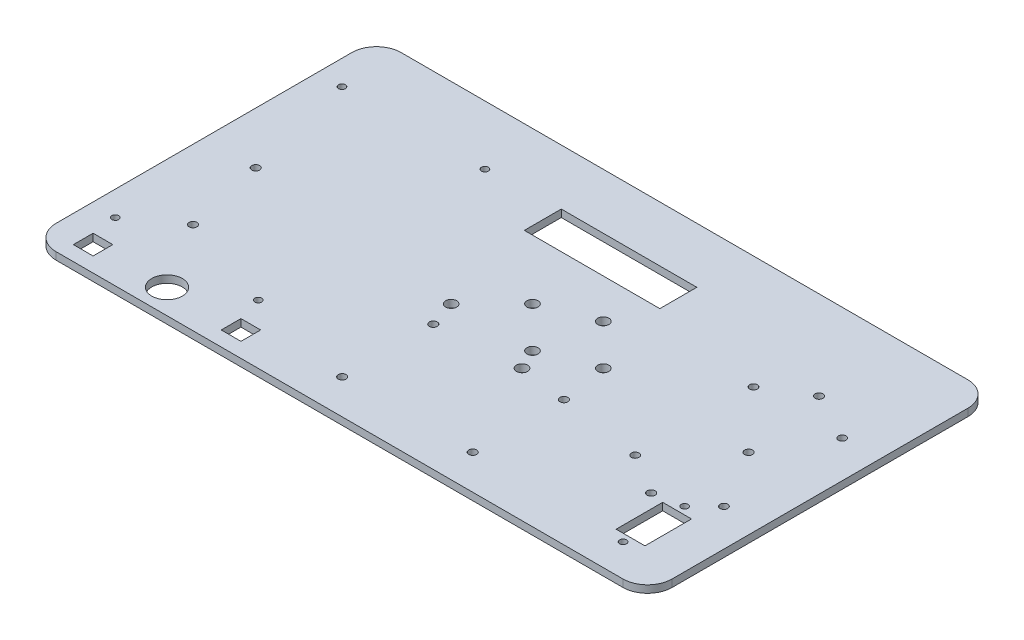
SolidWorks part; units mm, degrees
ref_plane "Front Plane" through (0, 0, 0) normal (0, 0, 1) x (1, 0, 0)
ref_plane "Top Plane" through (0, 0, 0) normal (0, 1, 0) x (1, 0, 0)
ref_plane "Right Plane" through (0, 0, 0) normal (1, 0, 0) x (0, 0, -1)
sketch "Sketch1" plane through (0, 0, 0) normal (0, 1, 0) x (1, 0, 0)
  line L1 (125, -70) -> (-125, -70)
  line L2 (125, -70) -> (125, 70)
  line L3 (125, 70) -> (-125, 70)
  line L4 (-125, -70) -> (-125, 70)
  line L5 (125, -70) -> (-125, 70) construction
  line L6 (125, 70) -> (-125, -70) construction
  point P0 (0, 0)
extrude "Boss-Extrude1" add sketch "Sketch1" along normal blind 3 contours L3 L4 L1 L2
fillet "Fillet2" radius 10 4 edges at (-125, 1.5, 70) (125, 1.5, 70) (-125, 1.5, -70) (125, 1.5, -70)
sketch "Sketch2" plane through (0, 0, 0) normal (0, 1, 0) x (1, 0, 0)
  line L0 (-125, 0) -> (125, 0)
  line L1 (-125, -60) -> (-125, 60) construction
  line L2 (125, -60) -> (125, 60) construction
  line L3 (110, -24) -> (110, 24)
  line L4 (-115, -46) -> (-115, 46)
  line L5 (110, 24) -> (74, 24)
  line L6 (110, 24) -> (110, -24)
  line L7 (110, -24) -> (74, -24)
  line L8 (74, 24) -> (74, -24)
  line L14 (0, 0.0606) -> (0, -55.9394)
  line L15 (37, -16.4394) -> (37, 16.5606)
  line L17 (96, 0) -> (-104, 0)
  line L18 (0, 0.0606) -> (37, 0.0606)
  line L20 (0, -55.9394) -> (-13, -55.9394)
  line L22 (0, -55.9394) -> (40, -55.9394)
  line L23 (-13, -55.9394) -> (-13, -18.9394)
  line L24 (37, 16.5606) -> (20.5, 16.5606)
  line L25 (-13, -18.9394) -> (40, -18.9394)
  line L26 (-13, -18.9394) -> (-13, -55.9394)
  line L27 (-13, -55.9394) -> (40, -55.9394)
  line L28 (40, -18.9394) -> (40, -55.9394)
  line L29 (37, 16.5606) -> (37, -16.4394)
  line L30 (37, -16.4394) -> (20.5, -16.4394)
  line L31 (20.5, 16.5606) -> (20.5, -16.4394)
  line L32 (0, -8.1894) -> (0, 8.3106)
  line L33 (16.5, 8.3106) -> (-16.5, 8.3106)
  line L34 (-115, 46) -> (-57, 46)
  line L35 (-115, 46) -> (-115, -46)
  line L36 (-115, -46) -> (-57, -46)
  line L37 (-57, 46) -> (-57, -46)
  line L39 (16.5, -8.1894) -> (-16.5, -8.1894)
  line L40 (16.5, -8.1894) -> (16.5, 8.3106)
  line L41 (16.5, 8.3106) -> (-16.5, 8.3106)
  line L42 (-16.5, -8.1894) -> (-16.5, 8.3106)
  line L43 (16.5, -8.1894) -> (-16.5, 8.3106) construction
  line L44 (16.5, 8.3106) -> (-16.5, -8.1894) construction
  circle A0 centre (110, 24) radius 1.55
  circle A1 centre (74, 24) radius 1.55
  circle A2 centre (74, -24) radius 1.55
  circle A3 centre (110, -24) radius 1.55
  circle A8 centre (-13, -18.9394) radius 1.6
  circle A9 centre (-13, -55.9394) radius 1.6
  circle A10 centre (40, -18.9394) radius 1.6
  circle A11 centre (40, -55.9394) radius 1.6
  circle A12 centre (37, 0.0606) radius 2.25
  circle A13 centre (20.5, 16.5606) radius 2.25
  circle A14 centre (20.5, -16.4394) radius 2.25
  circle A15 centre (96, 0) radius 1.6
  circle A16 centre (-104, 0) radius 1.6
  circle A17 centre (-115, 46) radius 1.4
  circle A18 centre (-57, 46) radius 1.4
  circle A19 centre (-57, -46) radius 1.4
  circle A20 centre (-115, -46) radius 1.4
  circle A21 centre (-16.5, -8.1894) radius 2.25
  circle A22 centre (16.5, -8.1894) radius 2.25
  circle A23 centre (0, 8.3106) radius 2.25
  point P6 (110, 0)
  point P10 (110, 0)
  point P16 (-115, 0)
  point P20 (-115, 0)
  point P25 (-115, 0)
  point P26 (74, 0)
  point P41 (37, 0.0606)
  point P46 (96, 0)
  point P55 (0, 0.0606)
  point P58 (0, 8.3106)
  dimension "D1" = 200
  dimension "D2" = 53
  dimension "D3" = 37
  dimension "D4" = 48
  dimension "D5" = 36
  dimension "D6" = 16.5
  dimension "D7" = 33
sketch "Sketch3" plane through (0, 0, 0) normal (0, 1, 0) x (1, 0, 0)
  line L1 (115, -70) -> (-115, -70) construction
  line L2 (-125, -60) -> (-125, 60) construction
  circle A3 centre (-104, 0) radius 33.5
  circle A4 centre (96, 0) radius 195.5
  circle A5 centre (-96.745, -32.705) radius 1.6
  point P6 (-338.6726, 198.929)
  point P7 (-96.745, -32.705)
  dimension "D1" = 37.295
  dimension "D2" = 28.255
sketch "Sketch4" plane through (0, 3, 0) normal (0, 1, 0) x (1, 0, 0)
  line L2 (115, -70) -> (-115, -70) construction
  line L3 (125, -60) -> (125, 60) construction
  line L4 (115, 70) -> (-115, 70) construction
  circle A4 centre (96, 0) radius 34.5
  circle A5 centre (-104, 0) radius 197.5
  circle A6 centre (90.54, -34.0652) radius 1.6
  circle A7 centre (90.54, 34.0652) radius 1.6
  point P4 (90.54, 34.0652)
  point P5 (90.54, 34.0652)
  point P6 (90.54, 34.0652)
  point P7 (96, 0)
  point P8 (90.54, 34.0652)
  point P9 (-104, 0)
  point P10 (90.54, 34.0652)
  point P11 (90.54, 34.0652)
  point P13 (90.54, -34.0652)
  dimension "D1" = 35.9348
  dimension "D2" = 34.46
  dimension "D3" = 34.46
  dimension "D4" = 35.9348
sketch "Sketch5" plane through (0, 3, 0) normal (0, 1, 0) x (1, 0, 0)
  line L0 (110, -24) -> (110, -58)
  line L1 (94, -44.446) -> (110, -44.446)
  line L2 (110, -58) -> (94, -58)
  line L3 (110, -58) -> (110, -30.892)
  line L4 (110, -30.892) -> (94, -30.892)
  line L5 (94, -58) -> (94, -30.892)
  line L6 (102, -31.946) -> (102, -56.946)
  line L7 (-125, -60) -> (-80, -60)
  line L8 (107.85, -53.896) -> (96.15, -53.896)
  line L9 (107.85, -53.896) -> (107.85, -34.996)
  line L10 (107.85, -34.996) -> (96.15, -34.996)
  line L11 (96.15, -53.896) -> (96.15, -34.996)
  line L12 (107.85, -53.896) -> (96.15, -34.996) construction
  line L13 (107.85, -34.996) -> (96.15, -53.896) construction
  line L14 (0, 70) -> (0, 40)
  line L15 (115, 70) -> (-115, 70) construction
  line L16 (-80, -60) -> (-50, -60)
  line L17 (-27.5, 47.5) -> (27.5, 47.5)
  line L18 (-27.5, 47.5) -> (-27.5, 32.5)
  line L19 (-27.5, 32.5) -> (27.5, 32.5)
  line L20 (27.5, 47.5) -> (27.5, 32.5)
  line L21 (-27.5, 47.5) -> (27.5, 32.5) construction
  line L22 (-27.5, 32.5) -> (27.5, 47.5) construction
  line L24 (-114, -56) -> (-106, -56)
  line L25 (-114, -56) -> (-114, -64)
  line L26 (-114, -64) -> (-106, -64)
  line L27 (-106, -56) -> (-106, -64)
  line L28 (-114, -56) -> (-106, -64) construction
  line L29 (-114, -64) -> (-106, -56) construction
  line L30 (-54, -56) -> (-46, -56)
  line L31 (-54, -56) -> (-54, -64)
  line L32 (-54, -64) -> (-46, -64)
  line L33 (-46, -56) -> (-46, -64)
  line L34 (-54, -56) -> (-46, -64) construction
  line L35 (-54, -64) -> (-46, -56) construction
  circle A0 centre (102, -31.946) radius 1.4
  circle A1 centre (102, -56.946) radius 1.4
  circle A3 centre (-80, -60) radius 6.2
  point P11 (102, -44.446)
  point P13 (102, -44.446)
  point P31 (-110, -60)
  point P34 (-110, -60)
extrude "Cut-Extrude5" cut sketch "Sketch2" against normal blind 7 and the other way blind 7 contours A17 | A18 | A20 | A19 | A16 | A23 | A21 | A22 | A13 | A12 | A10 | A14 | A8 | A9 | A11 | A1 | A0 | A15 | A3 | A2
extrude "Cut-Extrude6" cut sketch "Sketch3" against normal blind 7 and the other way blind 7 contours A5
extrude "Cut-Extrude7" cut sketch "Sketch4" against normal blind 7 and the other way blind 7 contours A7 | A6
extrude "Cut-Extrude8" cut sketch "Sketch5" against normal blind 7 and the other way blind 7 contours L20 L17 L18 L19 | L24 L27 L26 L25 | A3 | L30 L33 L32 L31 | A0 | A1 | L10 L11 L8 L9 region at (-13.75, 3, -46.9299)
